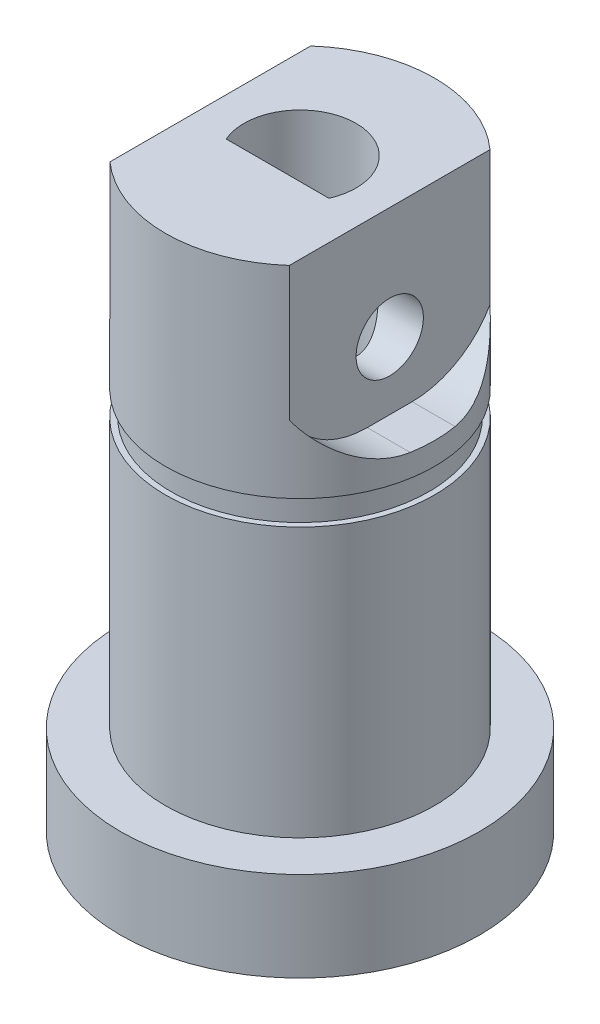
SolidWorks part; units mm, degrees
ref_plane "Front Plane" through (0, 0, 0) normal (0, 0, 1) x (1, 0, 0)
ref_plane "Top Plane" through (0, 0, 0) normal (0, 1, 0) x (1, 0, 0)
ref_plane "Right Plane" through (0, 0, 0) normal (1, 0, 0) x (0, 0, -1)
sketch "Sketch2" plane through (0, 0, 0) normal (0, 0, 1) x (1, 0, 0)
  line L0 (0, 0) -> (0, 26.1) construction
  line L19 (0, 26.1) -> (-6, 26.1)
  line L20 (-6, 26.1) -> (-6, 17.1)
  line L21 (-6, 17.1) -> (-5.75, 17.1)
  line L22 (-5.75, 17.1) -> (-5.75, 16)
  line L23 (-5.75, 16) -> (-6, 16)
  line L24 (-6, 16) -> (-6, 4)
  line L25 (-6, 4) -> (-8, 4)
  line L26 (-8, 4) -> (-8, 0)
  line L27 (-8, 0) -> (-7, 0)
  line L28 (-7, 0) -> (-7, 1.8)
  line L29 (-7, 1.8) -> (0, 1.8)
  line L31 (0, 1.8) -> (0, 26.1)
  line L40 (-6, 4) -> (-10.5, 4) construction
  line L41 (-6, 4) -> (-6, 9) construction
  line L42 (-6, 9) -> (-10.5, 9) construction
  line L43 (-10.5, 4) -> (-10.5, 9) construction
  line L44 (-6, 16) -> (-10.5, 16) construction
  line L45 (-6, 16) -> (-6, 11) construction
  line L46 (-6, 11) -> (-10.5, 11) construction
  line L47 (-10.5, 16) -> (-10.5, 11) construction
  dimension "D1" = 12
  dimension "D2" = 10.5
  dimension "D3" = 5
  dimension "D4" = 5
  dimension "D5" = 16
  dimension "D6" = 14
  dimension "D8" = 1.8
  dimension "D9" = 1.1
  dimension "D10" = 11.5
  dimension "D11" = 9
  dimension "D12" = 4
  dimension "D13" = 12
revolve "Revolve1" add sketch "Sketch2" angle 360 about L0
ref_plane "Plane1" through (-6, 0, 0) normal (-1, 0, 0) x (0, 0, 1)
sketch "Sketch3" plane through (-6, 0, 0) normal (-1, 0, 0) x (0, 0, 1)
  line L0 (0, 26.1) -> (0, 9.9472) construction
  line L1 (6, 26.1) -> (-6, 26.1) construction
  line L2 (9, 26.1) -> (-9, 26.1)
  line L3 (-1, 18.1) -> (1, 18.1)
  arc A0 (-9, 26.1) -> (-5, 22.1) centre (-9, 22.1) cw
  arc A1 (-5, 22.1) -> (-1, 18.1) centre (-1, 22.1) ccw
  arc A2 (9, 26.1) -> (5, 22.1) centre (9, 22.1) ccw
  arc A3 (5, 22.1) -> (1, 18.1) centre (1, 22.1) cw
  point P13 (0, 18.1)
  dimension "D1" = 1
  dimension "D2" = 8
  dimension "D3" = 4
  dimension "D4" = 4
  dimension "D5" = 8
extrude "Cut-Extrude2" cut sketch "Sketch3" against normal blind 2 contours A0 A1 L3 A3 A2 L2
mirror "Mirror1" about plane through (0, 0, 0) normal (1, 0, 0) of "Cut-Extrude2"
sketch "Sketch4" plane through (-4, 0, 0) normal (-1, 0, 0) x (0, 0, 1)
  line L0 (1, 18.1) -> (-1, 18.1) construction
  circle A0 centre (0, 21.1) radius 1.5
  point P5 (0, 18.1)
  dimension "D1" = 3
  dimension "D2" = 3
extrude "Cut-Extrude3" cut sketch "Sketch4" against normal through all contours A0
sketch "Sketch5" plane through (0, 1.8, 0) normal (0, -1, 0) x (1, 0, 0)
  line L0 (-2.2913, 1) -> (2.2913, 1)
  circle A0 centre (0, 0) radius 2.5
  dimension "D1" = 5
  dimension "D2" = 1
extrude "Cut-Extrude4" cut sketch "Sketch5" against normal through all contours L0 A0 region at (0, 1.8, -0.5463)
